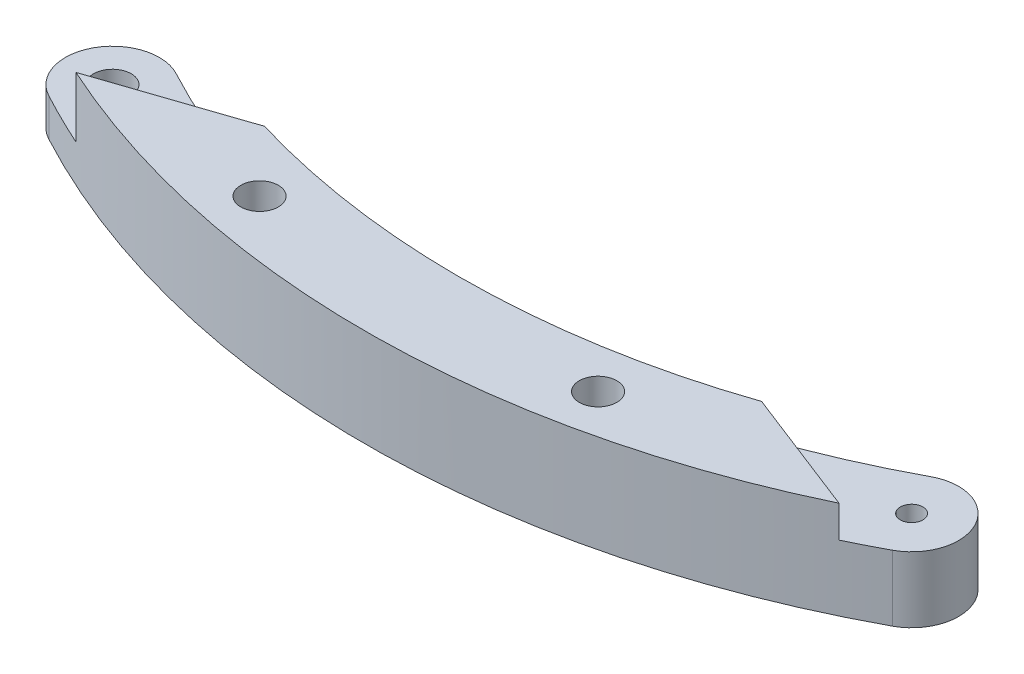
SolidWorks part; units mm, degrees
ref_plane "Front Plane" through (0, 0, 0) normal (0, 0, 1) x (1, 0, 0)
ref_plane "Top Plane" through (0, 0, 0) normal (0, 1, 0) x (1, 0, 0)
ref_plane "Right Plane" through (0, 0, 0) normal (1, 0, 0) x (0, 0, -1)
sketch "Sketch2" plane through (0, 0, 0) normal (0, 1, 0) x (1, 0, 0)
  arc A4 (0, 0) -> (42.5, 0) centre (21.25, -39.6666) cw construction
  arc A5 (1.1806, -2.2037) -> (41.3194, -2.2037) centre (21.25, -39.6666) cw
  arc A6 (-1.1806, 2.2037) -> (43.6806, 2.2037) centre (21.25, -39.6666) cw
  circle A7 centre (0, 0) radius 2.5
  circle A8 centre (42.5, 0) radius 2.5
  circle A9 centre (0, 0) radius 1
  circle A10 centre (42.5, 0) radius 0.6
  dimension "D1" = 2.5
  dimension "D3" = 45
  dimension "D4" = 42.5
  dimension "D5" = 1.2
  dimension "D6" = 2
  dimension "D2" = 2.5
extrude "Boss-Extrude2" add sketch "Sketch2" along normal blind 2 contours A8 A6 A7 A5 | A8 A10 | A7 A9 region at (21.25, 0, -3.8859) region at (-2.1414, 0, 1.1472) region at (40.3586, 0, -1.1472)
sketch "Sketch3" plane through (0, 2, 0) normal (0, 1, 0) x (1, 0, 0)
  line L0 (1.6703, 3.6103) -> (9.1577, 1.0768)
  line L1 (35.0535, 0.5293) -> (41.7986, 3.1587)
  arc A0 (41.3194, -2.2037) -> (1.1806, -2.2037) centre (21.25, -39.6666) ccw construction
  arc A1 (43.6806, 2.2037) -> (-1.1806, 2.2037) centre (21.25, -39.6666) ccw construction
  arc A10 (41.3194, -2.2037) -> (1.1806, -2.2037) centre (21.25, -39.6666) ccw
  arc A11 (41.3194, -2.2037) -> (43.6806, 2.2037) centre (42.5, 0) ccw
  arc A12 (43.6806, 2.2037) -> (-1.1806, 2.2037) centre (21.25, -39.6666) ccw
  arc A13 (-1.1806, 2.2037) -> (1.1806, -2.2037) centre (0, 0) ccw
  arc A14 (41.3194, -2.2037) -> (1.1806, -2.2037) centre (21.25, -39.6666) ccw
  arc A15 (41.3194, -2.2037) -> (43.6806, 2.2037) centre (42.5, 0) ccw
  arc A16 (43.6806, 2.2037) -> (-1.1806, 2.2037) centre (21.25, -39.6666) ccw
  arc A17 (-1.1806, 2.2037) -> (1.1806, -2.2037) centre (0, 0) ccw
  arc M7 (1.1806, -2.2037) -> (41.3194, -2.2037) centre (21.25, -39.6666) cw
  arc M9 (43.6806, 2.2037) -> (-1.1806, 2.2037) centre (21.25, -39.6666) ccw
  dimension "D3" = 0
extrude "Boss-Extrude3" add sketch "Sketch3" along normal blind 3.2 contours M9 M7 region at (21.9209, 2, -4.4096)
sketch "Sketch4" plane through (0, 2, 0) normal (0, 1, 0) x (1, 0, 0)
  line L1 (41.7986, 3.1587) -> (35.0535, 0.5293)
  line L2 (41.7986, 3.1587) -> (35.0535, 0.5293)
  arc A3 (41.3194, -2.2037) -> (35.0535, 0.5293) centre (21.25, -39.6666) ccw
  arc A4 (41.3194, -2.2037) -> (43.6806, 2.2037) centre (42.5, 0) ccw
  arc A5 (43.6806, 2.2037) -> (41.7986, 3.1587) centre (21.25, -39.6666) ccw
  arc A6 (41.3194, -2.2037) -> (35.0535, 0.5293) centre (21.25, -39.6666) ccw
  arc A7 (41.3194, -2.2037) -> (43.6806, 2.2037) centre (42.5, 0) ccw
  arc A8 (43.6806, 2.2037) -> (41.7986, 3.1587) centre (21.25, -39.6666) ccw
  circle M9 centre (42.5, 0) radius 0.6
  dimension "D1" = 0
extrude "Boss-Extrude4" add sketch "Sketch4" along normal blind 1.5 contours M9 | L2 A6 A7 A8 region at (42.5, 2, 0)
sketch "Sketch5" plane through (0, 5.2, 0) normal (0, 1, 0) x (1, 0, 0)
  circle A0 centre (12.25, 4.4242) radius 1
  circle A1 centre (30.25, 4.4242) radius 1
  arc A7 (0, 0) -> (42.5, 0) centre (21.25, -39.6666) cw construction
  dimension "D1" = 45
  dimension "D2" = 18
  dimension "D3" = 2
extrude "Cut-Extrude1" cut sketch "Sketch5" against normal through all
mirror "Mirror2" about plane through (0, 0, 0) normal (0, 0, 1) of bodies 105
delete or keep bodies "Body-Delete/Keep 1" type delete bodies bodies 105
